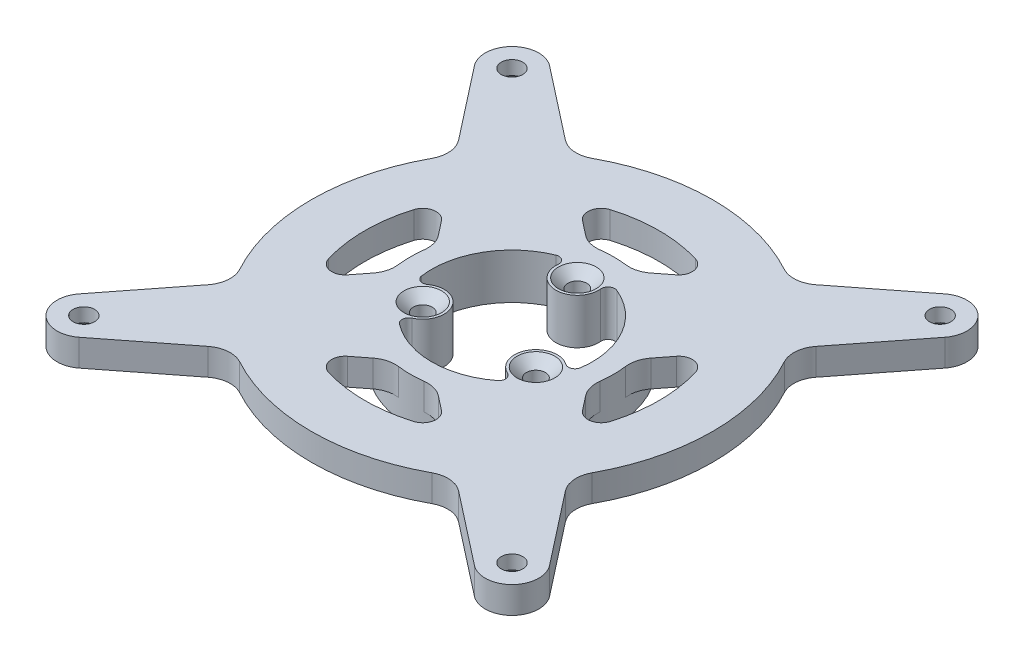
SolidWorks part; units mm, degrees
material "6061-T6 (SS)"
ref_plane "Front Plane" through (0, 0, 0) normal (0, 0, 1) x (1, 0, 0)
ref_plane "Top Plane" through (0, 0, 0) normal (0, 1, 0) x (1, 0, 0)
ref_plane "Right Plane" through (0, 0, 0) normal (1, 0, 0) x (0, 0, -1)
sketch "Sketch1" plane through (0, 0, 0) normal (0, 1, 0) x (1, 0, 0)
  circle A0 centre (0, 0) radius 22.225
  dimension "D1" = 44.45
extrude "Boss-Extrude1" add sketch "Sketch1" along normal blind 6.35
hole_wizard "CSK for M4 SFHCS1" positions "Sketch3" profile "Sketch2" countersink size "M4" standard "Ansi Metric" end condition through all
sketch "Sketch3" plane through (0, 6.35, 0) normal (0, 1, 0) x (-1, 0, 0)
  point P0 (0, -15.5)
  dimension "D1" = 15.5
sketch "Sketch2" plane through (0, 6.35, -15.5) normal (1, 0, 0) x (0, 0, 1)
  line L0 (0, 0) -> (0, 6.35)
  line L1 (0, 6.35) -> (2.25, 6.35)
  line L2 (2.25, 6.35) -> (2.25, 2.23)
  line L3 (2.25, 2.23) -> (4.48, 0)
  line L5 (4.48, 0) -> (0, 0)
  line L6 (-2.25, 2.23) -> (-4.48, 0) construction
  line L11 (0, -6.35) -> (0, 107.95) construction
  dimension "Thru Hole Dia." = 4.5
  dimension "Thru Hole Depth" = 6.35
  dimension "Near C'Sink Dia." = 8.96
  dimension "Near C'Sink Angle" = 90
pattern_circular "CirPattern1" count 3 over 360 about axis through (0, 6.35, 0) along (0, 1, 0) of "CSK for M4 SFHCS1"
sketch "Sketch4" plane through (0, 6.35, 0) normal (0, 1, 0) x (1, 0, 0)
  arc A0 (-11.641, -15.0795) -> (11.641, -15.0795) centre (0, 0) ccw
  arc A1 (-11.3263, -12.3769) -> (-16.3819, -3.6204) centre (-13.4234, -7.75) ccw
  circle A2 centre (0, 0) radius 19.05
  arc A3 (-7.2387, 17.6211) -> (-18.8797, -2.5417) centre (0, 0) ccw
  arc A4 (-5.0556, 15.9973) -> (5.0556, 15.9973) centre (0, 15.5) ccw
  arc A5 (16.3819, -3.6204) -> (11.3263, -12.3769) centre (13.4234, -7.75) ccw
  arc A6 (-5.0556, 15.9973) -> (-7.2387, 17.6211) centre (-6.6355, 16.1527) ccw
  arc A7 (7.2387, 17.6211) -> (5.0556, 15.9973) centre (6.6355, 16.1527) ccw
  arc A8 (-18.8797, -2.5417) -> (-16.3819, -3.6204) centre (-17.3064, -2.3299) ccw
  arc A9 (-11.3263, -12.3769) -> (-11.641, -15.0795) centre (-10.6709, -13.8228) ccw
  arc A10 (11.641, -15.0795) -> (11.3263, -12.3769) centre (10.6709, -13.8228) ccw
  arc A11 (16.3819, -3.6204) -> (18.8797, -2.5417) centre (17.3064, -2.3299) ccw
  arc A12 (18.8797, -2.5417) -> (7.2387, 17.6211) centre (0, 0) ccw
  dimension "D2" = 3.175
  dimension "D3" = 3.175
  dimension "D4" = 5.08
  dimension "D5" = 5.08
  dimension "D6" = 5.08
  dimension "D1" = 3.175
extrude "Cut-Extrude2" cut sketch "Sketch4" against normal through all
sketch "Sketch5" plane through (0, 6.35, 0) normal (0, 1, 0) x (1, 0, 0)
  line L1 (-57.15, -57.15) -> (57.15, -57.15)
  line L2 (-57.15, -57.15) -> (-57.15, 57.15)
  line L3 (-57.15, 57.15) -> (57.15, 57.15)
  line L4 (57.15, -57.15) -> (57.15, 57.15)
  line L5 (-57.15, -57.15) -> (57.15, 57.15) construction
  line L6 (-57.15, 57.15) -> (57.15, -57.15) construction
  circle A0 centre (0, 0) radius 22.225 construction
  circle A1 centre (0, 0) radius 22.225
  point P0 (0, 0)
  dimension "D1" = 114.3
  dimension "D2" = 114.3
extrude "Boss-Extrude2" add sketch "Sketch5" against normal up to surface (6.35 mm away) up to face at (0, 0, 0)
hole_wizard "CSK for #10 Flat Head Socket Cap Screw1" positions "Sketch7" profile "Sketch6" countersink size "#10" standard "Ansi Inch" end condition through all
sketch "Sketch7" plane through (0, 0, 0) normal (0, -1, 0) x (1, 0, 0)
  line L1 (-50.8, -50.8) -> (50.8, -50.8) construction
  line L2 (-50.8, -50.8) -> (-50.8, 50.8) construction
  line L3 (-50.8, 50.8) -> (50.8, 50.8) construction
  line L4 (50.8, -50.8) -> (50.8, 50.8) construction
  line L5 (-50.8, -50.8) -> (50.8, 50.8) construction
  line L6 (-50.8, 50.8) -> (50.8, -50.8) construction
  point P0 (50.8, -50.8)
  point P2 (0, 0)
  point P51 (-50.8, 50.8)
  point P53 (50.8, 50.8)
  point P55 (-50.8, -50.8)
  dimension "D1" = 101.6
  dimension "D2" = 101.6
sketch "Sketch6" plane through (50.8, 0, -50.8) normal (1, 0, 0) x (0, 0, -1)
  line L0 (0, 0) -> (0, 6.35)
  line L1 (0, 6.35) -> (2.5527, 6.35)
  line L2 (2.5527, 6.35) -> (2.5527, 3.068)
  line L3 (2.5527, 3.068) -> (5.2197, 0)
  line L5 (5.2197, 0) -> (0, 0)
  line L6 (-2.5527, 3.068) -> (-5.2197, 0) construction
  line L11 (0, -6.35) -> (0, 107.95) construction
  dimension "Thru Hole Dia." = 5.1054
  dimension "Thru Hole Depth" = 6.35
  dimension "Near C'Sink Dia." = 10.4394
  dimension "Near C'Sink Angle" = 82
sketch "Sketch8" plane through (0, 0, 0) normal (0, -1, 0) x (1, 0, 0)
  line L0 (57.15, 57.15) -> (-57.15, 57.15) construction
  line L1 (-55.8039, -46.8905) -> (-23.4882, -5.5283)
  line L2 (-50.8, -50.8) -> (0, 0) construction
  line L3 (-46.8905, -55.8039) -> (-5.5283, -23.4882)
  line L4 (0, 0) -> (-50.8, 50.8) construction
  line L5 (-55.8039, 46.8905) -> (-23.4882, 5.5283)
  line L6 (-46.8905, 55.8039) -> (-5.5283, 23.4882)
  line L7 (0, 24.13) -> (0, 57.15)
  line L8 (0, -24.13) -> (0, -57.15)
  line L9 (-57.15, -57.15) -> (57.15, -57.15) construction
  arc A0 (-46.8905, 55.8039) -> (-55.8039, 46.8905) centre (-50.8, 50.8) ccw
  arc A1 (0, 24.13) -> (-5.5283, 23.4882) centre (0, 0) ccw
  arc A2 (11.641, 15.0795) -> (-11.641, 15.0795) centre (0, 0) ccw construction
  circle A3 centre (50.8, 50.8) radius 6.35
  circle A4 centre (50.8, -50.8) radius 6.35
  arc A5 (-55.8039, -46.8905) -> (-46.8905, -55.8039) centre (-50.8, -50.8) ccw
  arc A6 (-23.4882, 5.5283) -> (-23.4882, -5.5283) centre (0, 0) ccw
  arc A7 (-5.5283, -23.4882) -> (0, -24.13) centre (0, 0) ccw
  line M2 (57.15, 57.15) -> (-57.15, 57.15)
  line M3 (-57.15, 57.15) -> (-57.15, -57.15)
  line M4 (-57.15, -57.15) -> (57.15, -57.15)
  dimension "D1" = 5.08
  dimension "D2" = 7
  dimension "D3" = 7
  dimension "D4" = 7
  dimension "D5" = 7
extrude "Cut-Extrude3" cut sketch "Sketch8" against normal through all contours A1 L7 A0 L6 M2 | A6 L5 A0 A5 L1 M3 | A0 M2 M3 | A5 M3 M4 | A7 L3 A5 L8 M4 region at (-44.8454, 0, 0) region at (-16.4482, 0, -44.8454) region at (-55.7316, 0, -55.7316) region at (-16.4482, 0, 44.8454) region at (-55.7316, 0, 55.7316)
mirror "Mirror1" about plane through (0, 0, 0) normal (1, 0, 0) of "Cut-Extrude3"
fillet "Fillet1" radius 6.35 8 edges at (-5.5283, 3.175, 23.4882) (5.5283, 3.175, 23.4882) (23.4882, 3.175, 5.5283) (23.4882, 3.175, -5.5283) (5.5283, 3.175, -23.4882) (-5.5283, 3.175, -23.4882) (-23.4882, 3.175, -5.5283) (-23.4882, 3.175, 5.5283)
sketch "Sketch9" plane through (0, 0, 0) normal (0, -1, 0) x (1, 0, 0)
  circle A0 centre (0, 0) radius 24.13
  arc A1 (3.0485, 23.9367) -> (-3.0485, 23.9367) centre (0, 0) ccw construction
  arc A2 (11.641, 15.0795) -> (-11.641, 15.0795) centre (0, 0) ccw construction
  arc A3 (11.641, 15.0795) -> (-11.641, 15.0795) centre (0, 0) ccw
  arc A4 (-11.641, 15.0795) -> (-11.3263, 12.3769) centre (-10.6709, 13.8228) ccw construction
  arc A5 (-16.3819, 3.6204) -> (-11.3263, 12.3769) centre (-13.4234, 7.75) ccw construction
  arc A6 (-16.3819, 3.6204) -> (-18.8797, 2.5417) centre (-17.3064, 2.3299) ccw construction
  arc A7 (-18.8797, 2.5417) -> (-7.2387, -17.6211) centre (0, 0) ccw construction
  arc A8 (-7.2387, -17.6211) -> (-5.0556, -15.9973) centre (-6.6355, -16.1527) ccw construction
  arc A9 (5.0556, -15.9973) -> (-5.0556, -15.9973) centre (0, -15.5) ccw construction
  arc A10 (7.2387, -17.6211) -> (18.8797, 2.5417) centre (0, 0) ccw construction
  arc A11 (5.0556, -15.9973) -> (7.2387, -17.6211) centre (6.6355, -16.1527) ccw construction
  arc A12 (18.8797, 2.5417) -> (16.3819, 3.6204) centre (17.3064, 2.3299) ccw construction
  arc A13 (11.3263, 12.3769) -> (16.3819, 3.6204) centre (13.4234, 7.75) ccw construction
  arc A14 (11.3263, 12.3769) -> (11.641, 15.0795) centre (10.6709, 13.8228) ccw construction
  arc A15 (-11.641, 15.0795) -> (-11.3263, 12.3769) centre (-10.6709, 13.8228) ccw
  arc A16 (-16.3819, 3.6204) -> (-11.3263, 12.3769) centre (-13.4234, 7.75) ccw
  arc A17 (-16.3819, 3.6204) -> (-18.8797, 2.5417) centre (-17.3064, 2.3299) ccw
  arc A18 (-18.8797, 2.5417) -> (-7.2387, -17.6211) centre (0, 0) ccw
  arc A19 (-7.2387, -17.6211) -> (-5.0556, -15.9973) centre (-6.6355, -16.1527) ccw
  arc A20 (5.0556, -15.9973) -> (-5.0556, -15.9973) centre (0, -15.5) ccw
  arc A21 (7.2387, -17.6211) -> (18.8797, 2.5417) centre (0, 0) ccw
  arc A22 (5.0556, -15.9973) -> (7.2387, -17.6211) centre (6.6355, -16.1527) ccw
  arc A23 (18.8797, 2.5417) -> (16.3819, 3.6204) centre (17.3064, 2.3299) ccw
  arc A24 (11.3263, 12.3769) -> (16.3819, 3.6204) centre (13.4234, 7.75) ccw
  arc A25 (11.3263, 12.3769) -> (11.641, 15.0795) centre (10.6709, 13.8228) ccw
  circle A26 centre (-13.4234, 7.75) radius 2.25 construction
  circle A27 centre (13.4234, 7.75) radius 2.25 construction
  circle A28 centre (0, -15.5) radius 2.25 construction
  circle A29 centre (-13.4234, 7.75) radius 2.25
  circle A30 centre (13.4234, 7.75) radius 2.25
  circle A31 centre (0, -15.5) radius 2.25
extrude "Boss-Extrude3" add sketch "Sketch9" along normal blind 4.445
sketch "Sketch10" plane through (0, 0, 0) normal (0, -1, 0) x (1, 0, 0)
  circle A0 centre (0, 0) radius 47.625
  circle A1 centre (0, 0) radius 34.925
  dimension "D1" = 95.25
  dimension "D2" = 69.85
extrude "Boss-Extrude4" add sketch "Sketch10" against normal up to surface (6.35 mm away) up to face at (0, 6.35, 0)
fillet "Fillet2" radius 3.175 8 edges at (31.29, 3.175, 15.5142) (31.29, 3.175, -15.5142) (15.5142, 3.175, -31.29) (-15.5142, 3.175, -31.29) (-31.29, 3.175, -15.5142) (-31.29, 3.175, 15.5142) (15.5142, 3.175, 31.29) (-15.5142, 3.175, 31.29)
fillet "Fillet3" radius 6.35 8 edges at (39.7102, 3.175, -26.2915) (39.7102, 3.175, 26.2915) (26.2915, 3.175, 39.7102) (-26.2915, 3.175, 39.7102) (-39.7102, 3.175, 26.2915) (-39.7102, 3.175, -26.2915) (-26.2915, 3.175, -39.7102) (26.2915, 3.175, -39.7102)
